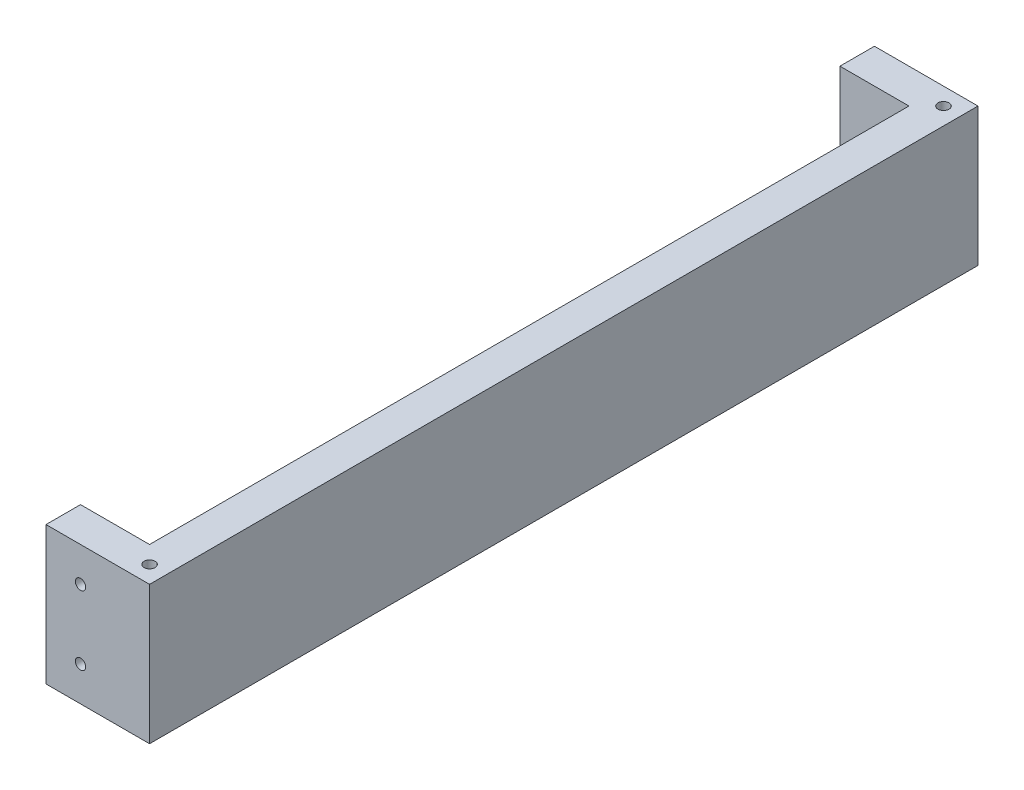
SolidWorks part; units mm, degrees
ref_plane "前视基准面" through (0, 0, 0) normal (0, 0, 1) x (1, 0, 0)
ref_plane "上视基准面" through (0, 0, 0) normal (0, 1, 0) x (1, 0, 0)
ref_plane "右视基准面" through (0, 0, 0) normal (1, 0, 0) x (0, 0, -1)
other "Configuration Table"
sketch "草图1" plane through (0, 0, 0) normal (0, 1, 0) x (1, 0, 0)
  line L5 (-1, -60) -> (1, -60)
  line L6 (-1, -60) -> (-1, 60)
  line L7 (-1, 60) -> (1, 60)
  line L8 (1, -60) -> (1, 60)
  line L9 (-1, -60) -> (1, 60) construction
  line L10 (-1, 60) -> (1, -60) construction
  point P0 (0, 0)
  dimension "D1" = 2
  dimension "D2" = 120
extrude "凸台-拉伸1" add sketch "草图1" along normal blind 2
sketch "草图3" plane through (1, 0, 0) normal (1, 0, 0) x (0, 0, -1)
  line L1 (-60, 0) -> (60, 0)
  line L2 (-60, 0) -> (-60, 20)
  line L3 (-60, 20) -> (60, 20)
  line L4 (60, 0) -> (60, 20)
  dimension "D1" = 20
extrude "凸台-拉伸3" add sketch "草图3" along normal blind 15
sketch "草图4" plane through (0, 0, 60) normal (0, 0, 1) x (1, 0, 0)
  line L1 (1, 20) -> (11, 20)
  line L2 (1, 20) -> (1, 9)
  line L3 (1, 9) -> (11, 9)
  line L4 (11, 20) -> (11, 9)
  dimension "D1" = 11
  dimension "D2" = 10
extrude "切除-拉伸1" cut sketch "草图4" against normal through all
sketch "草图5" plane through (0, 0, 0) normal (0, -1, 0) x (1, 0, 0)
  line L1 (1, 60) -> (-1, 60)
  line L2 (1, 60) -> (1, 43)
  line L3 (1, 43) -> (-1, 43)
  line L4 (-1, 60) -> (-1, 43)
  line L6 (-1, -60) -> (-1, 60) construction
  line L7 (-1, 60) -> (16, 60) construction
  line L9 (1, -60) -> (-1, -60)
  line L10 (1, -60) -> (1, -43)
  line L11 (1, -43) -> (-1, -43)
  line L12 (-1, -60) -> (-1, -43)
  line L13 (16, -60) -> (-1, -60) construction
  point P5 (0, 0)
  point P16 (0, 0)
  dimension "D1" = 2
  dimension "D2" = 17
extrude "切除-拉伸2" cut sketch "草图5" against normal through all
sketch "草图6" plane through (0, 9, 0) normal (0, 1, 0) x (1, 0, 0)
  line L0 (1, 60) -> (1, -60) construction
  line L1 (1, -55) -> (16, -55)
  line L2 (1, -55) -> (1, -60)
  line L3 (1, -60) -> (16, -60)
  line L4 (16, -55) -> (16, -60)
  line L5 (16, 60) -> (16, -60) construction
  line L6 (1, 60) -> (16, 60)
  line L7 (1, 60) -> (1, 55)
  line L8 (1, 55) -> (16, 55)
  line L9 (16, 60) -> (16, 55)
  dimension "D1" = 5
  dimension "D2" = 5
extrude "凸台-拉伸4" add sketch "草图6" along normal up to surface (11 mm away) up to face at (13.5, 20, 0)
sketch "草图7" plane through (0, 0, -60) normal (0, 0, -1) x (-1, 0, 0)
  line L0 (-6, 15) -> (-6, 5)
  line L1 (-1, 0) -> (-1, 20) construction
  line L2 (-16, 20) -> (-1, 20) construction
  line L3 (-16, 0) -> (-1, 0) construction
  line L4 (-16, 0) -> (-16, 20) construction
  circle A0 centre (-6, 15) radius 0.75
  circle A1 centre (-6, 5) radius 0.75
  dimension "D2" = 1.5
  dimension "D1" = 5
  dimension "D3" = 5
  dimension "D4" = 5
extrude "切除-拉伸3" cut sketch "草图7" against normal blind 2 contours A0 | A1
extrude "切除-拉伸4" cut sketch "草图7<3>" along normal blind 2 from surface contours A0 | A1 starting at face at (8.5, 10, 60)
sketch "草图7<3>" plane through (0, 0, -60) normal (0, 0, -1) x (-1, 0, 0) same geometry as "草图7"
sketch "草图8" plane through (0, 20, 0) normal (0, 1, 0) x (1, 0, 0)
  line L0 (16, -60) -> (1, -60) construction
  line L1 (16, 60) -> (16, -60) construction
  line L2 (16, 60) -> (1, 60) construction
  circle A0 centre (13.5, -57.5) radius 0.8
  circle A1 centre (13.5, 57.5) radius 0.8
  dimension "D3" = 1.6
  dimension "D1" = 2.5
  dimension "D2" = 2.5
  dimension "D4" = 2.5
  dimension "D5" = 2.5
extrude "切除-拉伸5" cut sketch "草图8" against normal blind 2
